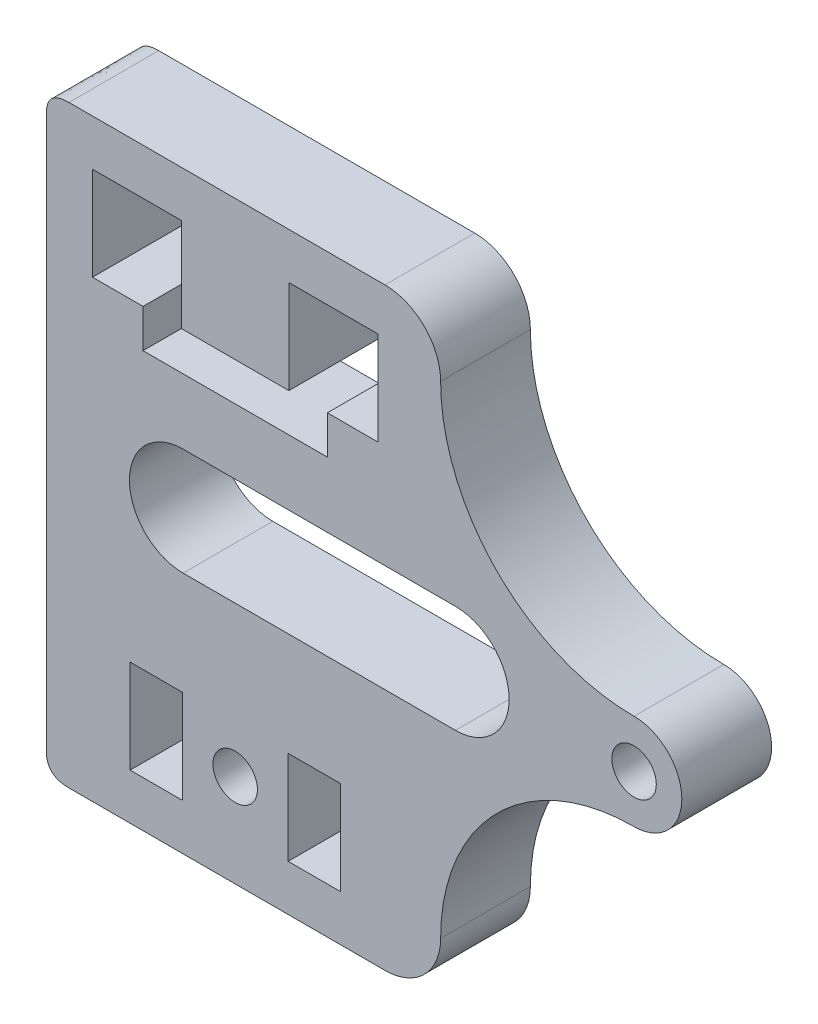
SolidWorks part; units mm, degrees
material "Acrylic (Medium-high impact)"
ref_plane "Front Plane" through (0, 0, 0) normal (0, 0, 1) x (1, 0, 0)
ref_plane "Top Plane" through (0, 0, 0) normal (0, 1, 0) x (1, 0, 0)
ref_plane "Right Plane" through (0, 0, 0) normal (1, 0, 0) x (0, 0, -1)
sketch "Sketch1" plane through (0, 0, 0) normal (0, 0, 1) x (1, 0, 0)
  line L0 (405.5669, 552.3889) -> (405.5669, 554.8889)
  line L1 (396.059, 554.8889) -> (403.059, 554.8889)
  line L2 (393.5512, 554.8889) -> (393.5512, 552.3889)
  line L3 (393.5512, 552.3889) -> (405.5669, 552.3889)
  line L4 (390.259, 560.9889) -> (390.259, 554.8889)
  line L5 (393.5512, 554.8889) -> (390.259, 554.8889)
  line L6 (396.059, 560.9889) -> (390.259, 560.9889)
  line L7 (396.059, 554.8889) -> (396.059, 560.9889)
  line L8 (405.5669, 554.8889) -> (408.859, 554.8889)
  line L9 (408.859, 554.8889) -> (408.859, 560.9889)
  line L10 (403.059, 560.9889) -> (403.059, 554.8889)
  line L11 (408.859, 560.9889) -> (403.059, 560.9889)
  line L12 (392.709, 534.3889) -> (392.709, 528.2889)
  line L13 (392.709, 528.2889) -> (396.109, 528.2889)
  line L14 (396.109, 534.3889) -> (392.709, 534.3889)
  line L15 (396.109, 528.2889) -> (396.109, 534.3889)
  line L16 (403.009, 528.2889) -> (406.4091, 528.2889)
  line L17 (406.4091, 528.2889) -> (406.4091, 534.3889)
  line L18 (403.009, 534.3889) -> (403.009, 528.2889)
  line L19 (406.4091, 534.3889) -> (403.009, 534.3889)
  line L20 (388.7268, 563.9889) -> (409.3246, 563.9889)
  line L21 (387.259, 562.5227) -> (387.259, 526.7551)
  line L22 (388.7268, 525.2889) -> (409.3246, 525.2889)
  line L23 (-605.591, 534.3889) -> (49394.409, 534.3889) construction
  line L24 (396.1657, 548.1389) -> (413.9157, 548.1389)
  line L25 (396.1657, 541.1389) -> (413.9157, 541.1389)
  line L26 (-600.441, 544.6389) -> (49399.559, 544.6389) construction
  line L27 (398.109, 531.3389) -> (396.109, 531.3389) construction
  line L28 (401.009, 531.3389) -> (403.009, 531.3389) construction
  line L29 (399.559, -466.6171) -> (399.559, 49533.3829) construction
  line L30 (425.559, -455.7473) -> (425.559, 49544.2527) construction
  line L31 (-608.8734, 554.8889) -> (49391.1266, 554.8889) construction
  line L32 (421.909, 544.6389) -> (421.909, 534.3889) construction
  line L33 (421.909, 544.6389) -> (421.909, 554.8889) construction
  line L34 (412.9514, 560.3621) -> (412.9514, 528.9157) construction
  circle A0 centre (425.559, 544.6389) radius 1.45
  arc A1 (396.1657, 548.1389) -> (396.1657, 541.1389) centre (396.1657, 544.6389) ccw
  circle A2 centre (399.559, 531.3389) radius 1.45
  arc A3 (412.9514, 528.9157) -> (425.559, 541.5233) centre (425.559, 528.9157) cw
  arc A4 (412.9514, 560.3621) -> (425.559, 547.7545) centre (425.559, 560.3621) ccw
  arc A5 (425.559, 547.7545) -> (425.559, 541.5233) centre (425.559, 544.6389) cw
  arc A7 (413.9157, 548.1389) -> (413.9157, 541.1389) centre (413.9157, 544.6389) cw
  arc A8 (409.3246, 525.2889) -> (412.9514, 528.9157) centre (409.3246, 528.9157) ccw
  arc A9 (409.3246, 563.9889) -> (412.9514, 560.3621) centre (409.3246, 560.3621) cw
  spline S36 degree 2 poles (387.259, 562.5227) (387.1783, 563.9889) (388.7268, 563.9889) knots 0 0 0 1 1 1
  spline S37 degree 2 poles (387.259, 526.7551) (387.1783, 525.2889) (388.7268, 525.2889) knots 0 0 0 1 1 1
  point P26 (399.559, 544.6389)
  point P30 (399.559, 554.8889)
  point P38 (394.409, 534.3889)
  point P40 (412.9514, 544.6389)
  dimension "D5" = 2.9
  dimension "D12" = 6.1
  dimension "D16" = 3.5
  dimension "D2" = 3.4
  dimension "D3" = 5.8
  dimension "D4" = 6.1
  dimension "D6" = 26
  dimension "D7" = 3.5
  dimension "D8" = 3
  dimension "D9" = 3
  dimension "D10" = 3
  dimension "D11" = 7
  dimension "D14" = 38.7
  dimension "D15" = 31.4465
  dimension "D17" = 17.75
  dimension "D19" = 13.3924
  dimension "D20" = 22.35
  dimension "D21" = 7
  dimension "Boss_height" = 18
  dimension "Boss_thickness" = 2.5
extrude "Boss-Extrude2" add sketch "Sketch1" along normal blind 5.85
sketch "Sketch2" plane through (0, 0, 0) normal (0, 0, 1) x (1, 0, 0)
  line L0 (-600.441, 531.3389) -> (49399.559, 531.3389) construction
  line L1 (406.4091, 528.2889) -> (406.4091, 534.3889) construction
  circle A0 centre (409.6591, 531.3389) radius 1.25
  point P5 (408.4091, 531.3389)
  dimension "D1" = 2.5
  dimension "D2" = 2
extrude "Cut-Extrude1" cut sketch "Sketch2" along normal blind 1
